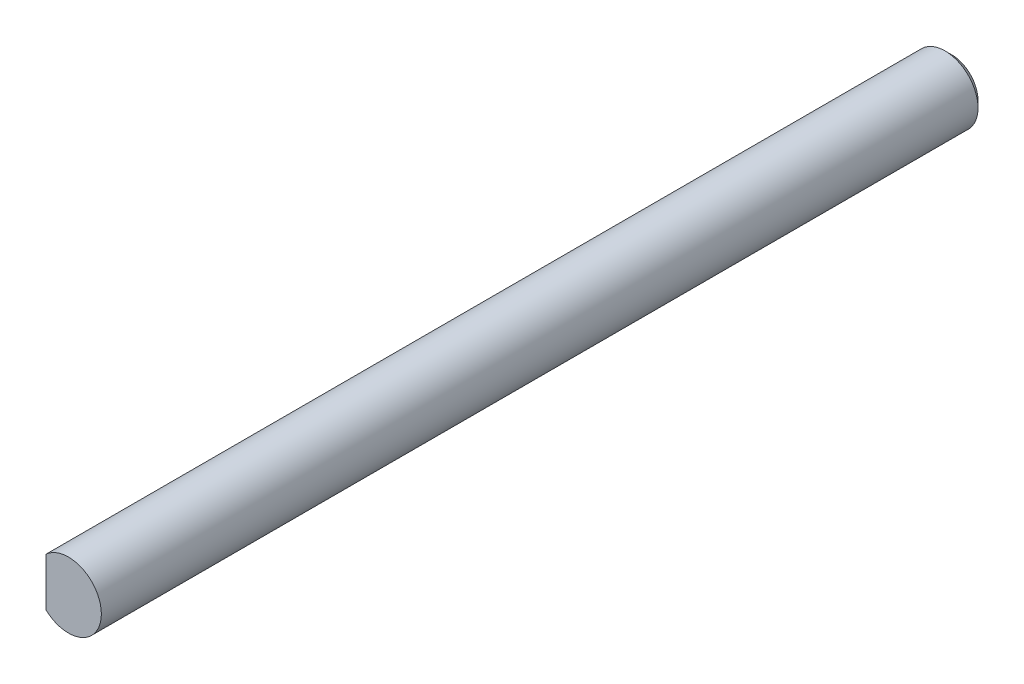
SolidWorks part; units mm, degrees
material "Acero aleado"
ref_plane "Alzado" through (0, 0, 0) normal (0, 0, 1) x (1, 0, 0)
ref_plane "Planta" through (0, 0, 0) normal (0, 1, 0) x (1, 0, 0)
ref_plane "Vista lateral" through (0, 0, 0) normal (1, 0, 0) x (0, 0, -1)
sketch "Croquis1" plane through (0, 0, 0) normal (0, 0, 1) x (1, 0, 0)
  circle A0 centre (0, 0) radius 2.5
  dimension "D1" = 5
extrude "Saliente-Extruir1" add sketch "Croquis1" along normal blind 67
sketch "Sketch1" plane through (0, 0, 67) normal (0, 0, 1) x (1, 0, 0)
  line L0 (-1.7, 1.833) -> (-1.7, -1.833)
  line L1 (-1.7, 0) -> (2.5, 0) construction
  arc A2 (-1.7, 1.833) -> (-1.7, -1.833) centre (0, 0) ccw
  circle A3 centre (0, 0) radius 2.5 construction
  dimension "D1" = 4.2
extrude "Cut-Extrude1" cut sketch "Sketch1" against normal blind 15
chamfer "Chamfer1" distance 0.5 angle 45 1 edges at (2.5, 0, 0)
